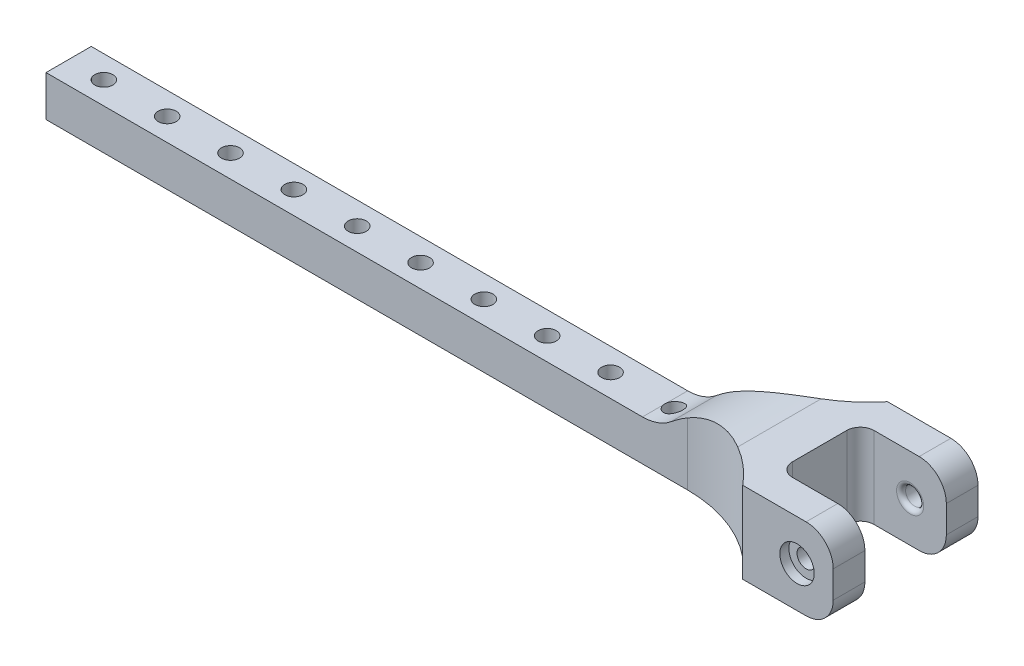
SolidWorks part; units mm, degrees
ref_plane "Front Plane" through (0, 0, 0) normal (0, 0, 1) x (1, 0, 0)
ref_plane "Top Plane" through (0, 0, 0) normal (0, 1, 0) x (1, 0, 0)
ref_plane "Right Plane" through (0, 0, 0) normal (1, 0, 0) x (0, 0, -1)
sketch "Sketch1" plane through (0, 0, 0) normal (0, 0, 1) x (1, 0, 0)
  line L0 (0, 0) -> (90, 0) construction
  line L1 (0, 4.5) -> (90, 4.5)
  line L2 (0, -4.5) -> (90, -4.5)
  line L3 (90, 4.5) -> (90, -4.5)
  circle A0 centre (0, 0) radius 1.1
  circle A2 centre (0, 0) radius 4.5
  dimension "D2" = 9
  dimension "D1" = 90
extrude "Boss-Extrude1" add sketch "Sketch1" along normal blind 5 contours A0 A2 | A2 L0 L1 | L0 A2 L2 region at (46.7613, 0, 0) region at (3.092, 3.092, 0)
sketch "Sketch2" plane through (0, 4.5, 0) normal (0, 1, 0) x (1, 0, 0)
  line L0 (90, -2.5) -> (100, -2.5) construction
  line L1 (90, -5) -> (90, 0) construction
  line L2 (100, 2) -> (90.5, 2)
  line L3 (90, 5.5) -> (100, 5.5)
  line L4 (90, 5.5) -> (90, -10.5)
  line L5 (90, -10.5) -> (100, -10.5)
  line L6 (100, 5.5) -> (100, -10.5)
  line L7 (90, 5.5) -> (100, -10.5) construction
  line L8 (90, -10.5) -> (100, 5.5) construction
  line L9 (90.5, 2) -> (90.5, -7)
  line L10 (90.5, -7) -> (100, -7)
  point P4 (95, -2.5)
  line M5 (90, -5) -> (90, 0)
  dimension "D1" = 16
  dimension "D2" = 3.5
  dimension "D3" = 9
  dimension "D4" = 10
  dimension "D5" = 9.5
  dimension "D6" = 10
  dimension "D7" = 10
extrude "Boss-Extrude2" add sketch "Sketch2" against normal blind 9 contours L10 L9 L2 L6 L3 L4 L5 M5 region at (95.25, 4.5, -2.1887)
fillet "Fillet1" radius 15 2 edges
sketch "Sketch3" plane through (0, 0, 10.5) normal (0, 0, 1) x (1, 0, 0)
  line L0 (90, 4.5) -> (100, 4.5) construction
  line L2 (90, -4.5) -> (90, 4.5) construction
  circle A0 centre (96, 0) radius 1
  dimension "D1" = 4.5
  dimension "D2" = 6
extrude "Cut-Extrude1" cut sketch "Sketch3" against normal blind 16
fillet "Fillet2" radius 3 4 edges at (100, 4.5, -3.75) (100, 4.5, 8.75) (100, -4.5, 8.75) (100, -4.5, -3.75)
sketch "Sketch4" plane through (0, 0, 10.5) normal (0, 0, 1) x (1, 0, 0)
  circle A0 centre (96, 0) radius 1.9
extrude "Cut-Extrude2" cut sketch "Sketch4" against normal blind 1
fillet "Fillet3" radius 1.5 2 edges at (90.5, 0, 7) (90.5, 0, -2)
fillet "Fillet4" radius 0.5 1 edges at (95, 0, -2)
sketch "Sketch5" plane through (0, 0, 5) normal (0, 0, 1) x (1, 0, 0)
  line L1 (78.3918, 4.5) -> (-4.5, 4.5)
  line L2 (78.3918, 4.5) -> (78.3918, 0)
  line L3 (78.3918, 0) -> (-4.5, 0)
  line L4 (-4.5, 4.5) -> (-4.5, 0)
  arc A0 (0, 4.5) -> (0, -4.5) centre (0, 0) ccw construction
extrude "Cut-Extrude3" cut sketch "Sketch5" against normal blind 5
sketch "Sketch6" plane through (0, 0, 0) normal (0, 1, 0) x (1, 0, 0)
  line L0 (78.3918, 0) -> (78.3918, -5) construction
  circle A0 centre (74.3918, -2.5) radius 1
  point P2 (78.3918, -2.5)
  dimension "D1" = 4
extrude "Cut-Extrude4" cut sketch "Sketch6" against normal blind 4.5
pattern_linear "LPattern1" count 11 spacing 7 along (-1, 0, 0) of "Cut-Extrude4"
fillet "Fillet5" radius 5 1 edges at (78.3918, 0, 2.5)
fillet "Fillet6" radius 15 1 edges at (78.3918, 4.5, 2.5)
sketch "Sketch7" plane through (0, 0, 0) normal (0, 1, 0) x (1, 0, 0)
  line L0 (1.1, -5) -> (73.4169, -5) construction
  line L1 (-4.5, 0) -> (7.5, 0)
  line L2 (-4.5, 0) -> (-4.5, -5)
  line L3 (-4.5, -5) -> (7.5, -5)
  line L4 (7.5, 0) -> (7.5, -5)
  dimension "D1" = 12
extrude "Cut-Extrude5" cut sketch "Sketch7" against normal blind 5
fillet "Fillet7" radius 0.5 2 edges at (97, 0, -5.5) (97, 0, 7)
